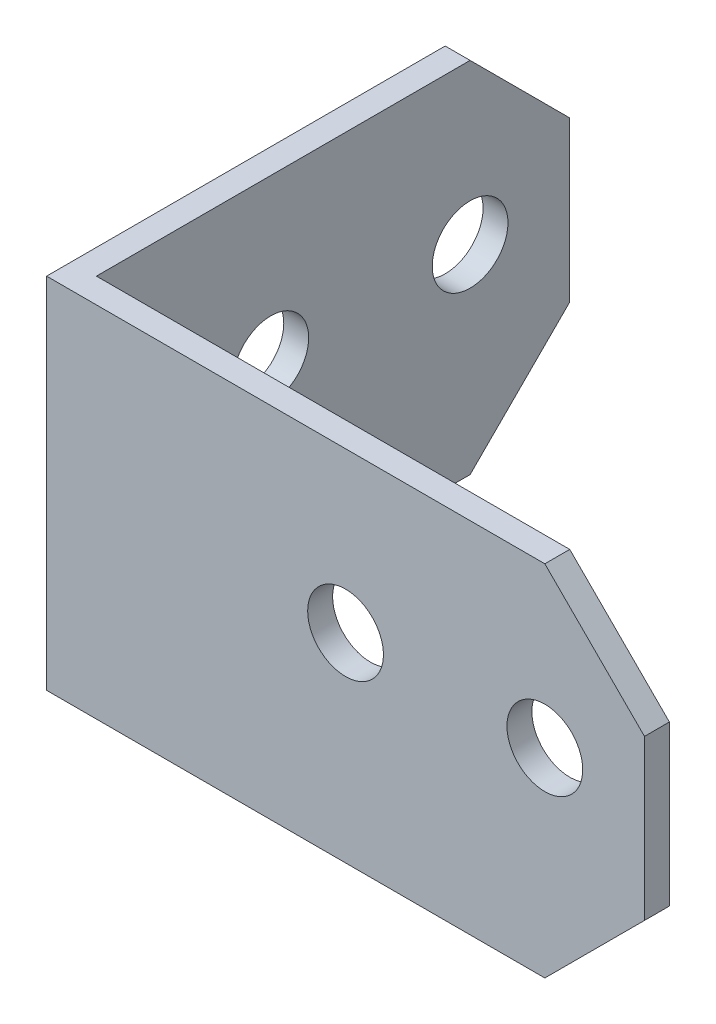
SolidWorks part; units mm, degrees
material "6061-T6 (SS)"
ref_plane "Front Plane" through (0, 0, 0) normal (0, 0, 1) x (1, 0, 0)
ref_plane "Top Plane" through (0, 0, 0) normal (0, 1, 0) x (1, 0, 0)
ref_plane "Right Plane" through (0, 0, 0) normal (1, 0, 0) x (0, 0, -1)
sketch "Sketch1" plane through (0, 0, 0) normal (0, 1, 0) x (1, 0, 0)
  line L1 (-18.1093, 25.3412) -> (-16.5218, 25.3412)
  line L2 (-18.1093, 25.3412) -> (-18.1093, -6.4088)
  line L4 (-16.5218, 25.3412) -> (-16.5218, -4.8213)
  line L5 (-18.1093, -6.4088) -> (19.9907, -6.4088)
  line L7 (-16.5218, -4.8213) -> (19.9907, -4.8213)
  line L8 (19.9907, -6.4088) -> (19.9907, -4.8213)
  dimension "D1" = 1.5875
  dimension "D2" = 1.5875
  dimension "D3" = 31.75
  dimension "D4" = 38.1
extrude "Boss-Extrude1" add sketch "Sketch1" along normal blind 45.72 contours L2 L5 L8 L7 L4 L1
sketch "Sketch2" plane through (0, 0, 4.8213) normal (0, 0, -1) x (-1, 0, 0)
  line L1 (-13.6407, 35.56) -> (-0.9407, 35.56) construction
  line L2 (-13.6407, 35.56) -> (-13.6407, 10.16) construction
  line L3 (-13.6407, 10.16) -> (-0.9407, 10.16) construction
  line L4 (-0.9407, 35.56) -> (-0.9407, 10.16) construction
  line L5 (18.1093, 45.72) -> (18.1093, 0) construction
  line L6 (16.5218, 45.72) -> (-19.9907, 45.72) construction
  circle A0 centre (-0.9407, 35.56) radius 2.413
  circle A1 centre (-13.6407, 35.56) radius 2.413
  circle A2 centre (-13.6407, 10.16) radius 2.413
  circle A3 centre (-0.9407, 10.16) radius 2.413
  dimension "D5" = 4.826
  dimension "D1" = 12.7
  dimension "D2" = 19.05
  dimension "D3" = 10.16
  dimension "D4" = 25.4
extrude "Cut-Extrude1" cut sketch "Sketch2" against normal through all
sketch "Sketch3" plane through (-16.5218, 0, 0) normal (1, 0, 0) x (0, 0, -1)
  line L0 (-6.4088, 45.72) -> (-6.4088, 0) construction
  line L1 (18.9912, 35.56) -> (6.2912, 35.56) construction
  line L2 (18.9912, 35.56) -> (18.9912, 10.16) construction
  line L3 (18.9912, 10.16) -> (6.2912, 10.16) construction
  line L4 (6.2912, 35.56) -> (6.2912, 10.16) construction
  line L5 (25.3412, 45.72) -> (-4.8213, 45.72) construction
  circle A0 centre (6.2912, 35.56) radius 2.413
  circle A1 centre (18.9912, 35.56) radius 2.413
  circle A2 centre (18.9912, 10.16) radius 2.413
  circle A3 centre (6.2912, 10.16) radius 2.413
  dimension "D5" = 4.826
  dimension "D1" = 12.7
  dimension "D2" = 25.4
  dimension "D3" = 10.16
  dimension "D4" = 12.7
extrude "Cut-Extrude2" cut sketch "Sketch3" against normal through all
chamfer "Chamfer1" distance 6.35 angle 45 4 edges at (19.9907, 45.72, 5.615) (19.9907, 0, 5.615) (-17.3155, 0, -25.3412) (-17.3155, 45.72, -25.3412)
sketch "Sketch4" plane through (0, 0, 4.8213) normal (0, 0, -1) x (-1, 0, 0)
  line L0 (-19.9907, 22.86) -> (16.5218, 22.86)
  line L1 (-19.9907, 39.37) -> (-19.9907, 6.35) construction
  line L2 (16.5218, 45.72) -> (16.5218, 0) construction
  line L3 (16.5218, 22.86) -> (16.5218, 0)
  line L4 (16.5218, 0) -> (-13.6407, 0)
  line L5 (-13.6407, 0) -> (-19.9907, 6.35)
  line L6 (-19.9907, 6.35) -> (-19.9907, 22.86)
sketch "Sketch5" plane through (-16.5218, 0, 0) normal (1, 0, 0) x (0, 0, -1)
  line L0 (25.3412, 22.86) -> (-4.8213, 22.86)
  line L1 (25.3412, 39.37) -> (25.3412, 6.35) construction
  line L2 (-4.8213, 22.86) -> (-4.8213, 0)
  line L3 (-4.8213, 0) -> (18.9912, 0)
  line L4 (18.9912, 0) -> (25.3412, 6.35)
  line L5 (25.3412, 6.35) -> (25.3412, 22.86)
extrude "Cut-Extrude3" cut sketch "Sketch4" against normal through all
extrude "Cut-Extrude4" cut sketch "Sketch5" against normal through all
sketch "Sketch6" plane through (0, 0, 6.4088) normal (0, 0, 1) x (1, 0, 0)
  line L0 (-18.1093, 45.72) -> (-18.1093, 0) construction
  line L1 (-18.1093, 22.86) -> (-16.5218, 22.86)
  line L2 (-18.1093, 22.86) -> (-18.1093, 0)
  line L3 (-18.1093, 0) -> (-16.5218, 0)
  line L4 (-16.5218, 22.86) -> (-16.5218, 0)
extrude "Cut-Extrude5" cut sketch "Sketch6" against normal through all
chamfer "Chamfer2" distance 6.35 angle 45 2 edges at (-17.3155, 22.86, -25.3412) (19.9907, 22.86, 5.615)
